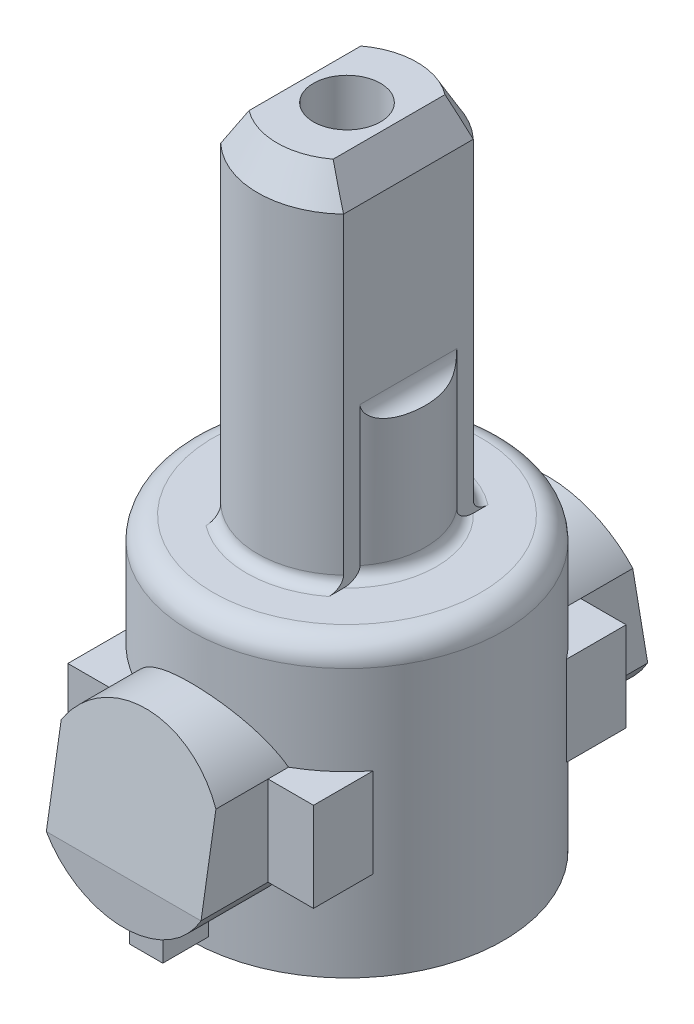
SolidWorks part; units mm, degrees
ref_plane "Front" through (0, 0, 0) normal (0, 0, 1) x (1, 0, 0)
ref_plane "Top" through (0, 0, 0) normal (0, 1, 0) x (1, 0, 0)
ref_plane "Right" through (0, 0, 0) normal (1, 0, 0) x (0, 0, -1)
sketch "Sketch1" plane through (0, 0, 0) normal (0, 1, 0) x (1, 0, 0)
  circle A0 centre (0, 0) radius 3.5
  dimension "D1" = 7
extrude "Extrude1" add sketch "Sketch1" along normal blind 3.5 and the other way blind 3
sketch "Sketch2" plane through (0, 0, 0) normal (0, 1, 0) x (1, 0, 0)
  line L0 (0, -998.3728) -> (0, 49001.6272) construction
  line L1 (0, -3.575) -> (0, 3.575) construction
  line L2 (-1004.1812, 0) -> (48995.8188, 0) construction
  line L3 (-3.575, 0) -> (3.575, 0) construction
  line L4 (2.75, 3.5) -> (-2.75, 3.5)
  line L5 (-2.75, 3.5) -> (-2.75, 2.1651)
  line L6 (2.75, 3.5) -> (2.75, 2.1651)
  line L7 (-2.75, 2.1651) -> (2.75, 2.1651)
  line L8 (-2.75, -3.5) -> (-2.75, -2.1651)
  line L9 (2.75, -3.5) -> (-2.75, -3.5)
  line L10 (2.75, -3.5) -> (2.75, -2.1651)
  line L11 (-2.75, -2.1651) -> (2.75, -2.1651)
  circle A0 centre (0, 0) radius 3.5 construction
  point P15 (0, 3.5)
  dimension "D1" = 5.5
extrude "Extrude2" add sketch "Sketch2" along normal mid plane 2
sketch "Sketch3" plane through (0, 0, 0) normal (0, 0, 1) x (1, 0, 0)
  line L0 (1.7321, 1) -> (1.7321, -1)
  line L1 (2.75, 1) -> (0, 1) construction
  line L2 (-1.7321, 1) -> (-1.7321, -1)
  line L3 (-2.75, -1) -> (0, -1) construction
  line L4 (-2.75, -1) -> (0, -1) construction
  arc A0 (1.7321, 1) -> (-1.7321, 1) centre (0, 0) ccw
  arc A1 (-1.7321, -1) -> (1.7321, -1) centre (0, 0) ccw
  dimension "D1" = 4
extrude "Extrude3" add sketch "Sketch3" along normal mid plane 10
sketch "Sketch4" plane through (0, 0, 0) normal (1, 0, 0) x (0, 0, -1)
  line L0 (-5, -1) -> (-4.5, 2)
  line L1 (-3.5, 2) -> (-5, 2) construction
  line L2 (-3.5, 3.5) -> (-3.5, 2) construction
  dimension "D1" = 1
extrude "Extrude4" cut sketch "Sketch4" against normal through all and the other way through all
mirror "Mirror1" about plane through (0, 0, 0) normal (0, 0, 1) of "Extrude4"
sketch "Sketch5" plane through (0, 0, 0) normal (1, 0, 0) x (0, 0, -1)
  line L0 (-3.5, -3) -> (3.5, -3) construction
  line L1 (-3.25, -1.75) -> (-4.5, -1.75)
  line L2 (-3.25, -1.75) -> (-3.25, -2.75)
  line L3 (-3.25, -2.75) -> (-4.5, -2.75)
  line L4 (-4.5, -1.75) -> (-4.5, -2.75)
  line L6 (3.25, -1.75) -> (4.5, -1.75)
  line L7 (3.25, -1.75) -> (3.25, -2.75)
  line L8 (3.25, -2.75) -> (4.5, -2.75)
  line L9 (4.5, -1.75) -> (4.5, -2.75)
  line L12 (-5, -2) -> (-3.5, -2) construction
  line L13 (-3.5, -2) -> (-3.5, -3) construction
  line L14 (3.5, -3) -> (3.5, -2) construction
  dimension "D1" = 0.25
  dimension "D2" = 1
  dimension "D3" = 0.25
  dimension "D4" = 0.25
  dimension "D5" = 0.25
extrude "Extrude7" add sketch "Sketch5" along normal mid plane 0.75
sketch "Sketch6" plane through (0, 3.5, 0) normal (0, 1, 0) x (1, 0, 0)
  line L0 (1.375, 1.4524) -> (1.375, -1.4524)
  line L1 (0, 2) -> (0, 0) construction
  line L2 (0, -3.575) -> (0, 3.575) construction
  line L3 (-1.375, 1.4524) -> (-1.375, -1.4524)
  arc A0 (1.375, 1.4524) -> (-1.375, 1.4524) centre (0, 0) ccw
  arc A1 (-1.375, -1.4524) -> (1.375, -1.4524) centre (0, 0) ccw
  dimension "D1" = 4
  dimension "D2" = 2.75
extrude "Extrude8" add sketch "Sketch6" along normal blind 8
chamfer "Chamfer1" distance 0.75 angle 30 4 edges at (1.375, 11.5, 0) (0, 11.5, 2) (-1.375, 11.5, 0) (0, 11.5, -2) first distance on face at (1.375, 7.5, 0) first distance on face at (0, 7.5, 1.7262) first distance on face at (-1.375, 7.5, 0) first distance on face at (0, 7.5, -1.7262)
sketch "Sketch7" plane through (0, 11.5, 0) normal (0, 1, 0) x (1, 0, 0)
  circle A0 centre (0, 0) radius 0.75
  dimension "D1" = 1.5
extrude "Extrude9" cut sketch "Sketch7" against normal blind 2
sketch "Sketch8" plane through (0, 3.5, 0) normal (0, 1, 0) x (1, 0, 0)
  circle A0 centre (0, 0) radius 1.75
  dimension "D1" = 3.5
extrude "Extrude10" add sketch "Sketch8" along normal blind 3
fillet "Fillet1" radius 0.375 2 edges at (1.375, 6.5, 0) (-1.375, 6.5, 0)
fillet "Fillet2" radius 0.25 4 edges at (-1.75, 3.5, 0) (0, 3.5, -2) (1.75, 3.5, 0) (0, 3.5, 2)
fillet "Fillet3" radius 0.5 1 edges at (0, 3.5, 3.5)
sketch "Sketch9" plane through (0, -3, 0) normal (0, -1, 0) x (1, 0, 0)
  circle A0 centre (0, 0) radius 3
  circle A1 centre (0, 0) radius 3.5 construction
  dimension "D1" = 0.5
extrude "Extrude11" cut sketch "Sketch9" against normal offset from surface (6 mm away) 0.5 up to face at (0, 3.5, 3)
fillet "Fillet4" radius 0.25 1 edges at (0, 3, 3)
sketch "Sketch10" plane through (0, 3, 0) normal (0, -1, 0) x (1, 0, 0)
  circle A0 centre (0, 0) radius 1
  dimension "D1" = 2
extrude "Extrude12" add sketch "Sketch10" along normal blind 7
sketch "Sketch11" plane through (0, -3, 0) normal (0, -1, 0) x (1, 0, 0)
  line L0 (2.9896, 0.25) -> (2.625, 0.25)
  line L1 (2.9896, -0.25) -> (2.625, -0.25)
  line L2 (2.625, 0.25) -> (2.625, -0.25)
  line L3 (-2.625, 0.25) -> (-2.625, -0.25)
  line L4 (-2.625, 0.25) -> (-2.9896, 0.25)
  line L5 (-2.625, -0.25) -> (-2.9896, -0.25)
  circle A0 centre (0, 0) radius 3 construction
  arc A1 (-2.9896, 0.25) -> (-2.9896, -0.25) centre (0, 0) ccw
  arc A2 (2.9896, -0.25) -> (2.9896, 0.25) centre (0, 0) ccw
  dimension "D1" = 5.25
  dimension "D2" = 0.5
extrude "Extrude13" add sketch "Sketch11" against normal up to body
chamfer "Chamfer2" distance 0.35 angle 45 2 edges at (2.625, -3, 0) (-2.625, -3, 0)
